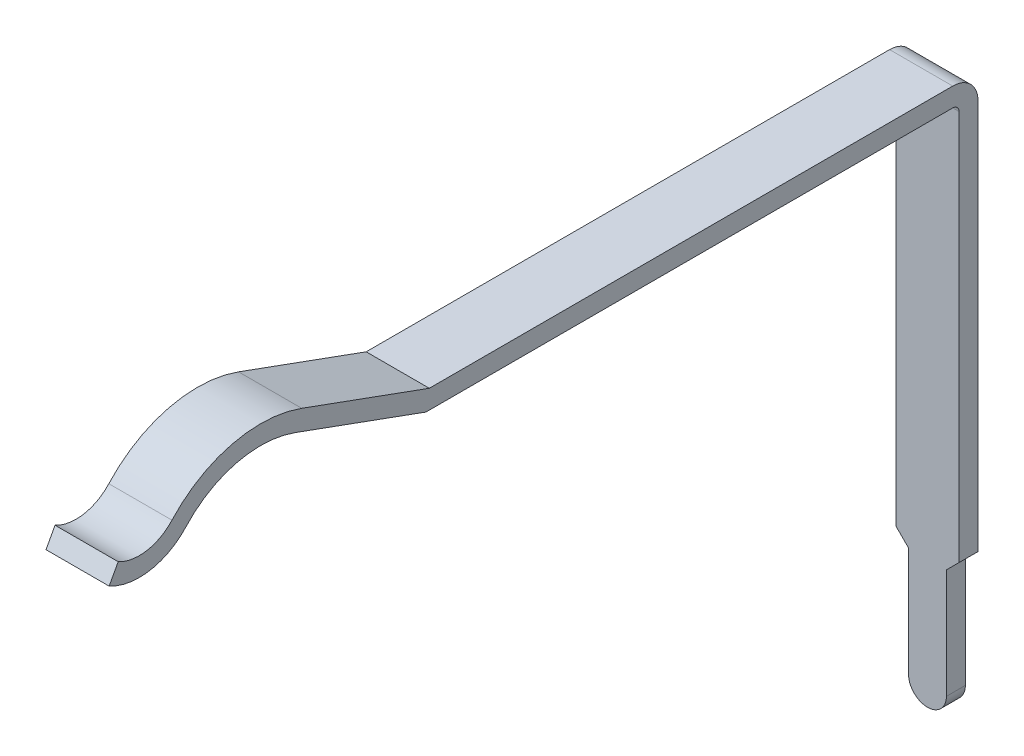
SolidWorks part; units mm, degrees
material "Pure Gold"
ref_plane "Front Plane" through (0, 0, 0) normal (0, 0, 1) x (1, 0, 0)
ref_plane "Top Plane" through (0, 0, 0) normal (0, 1, 0) x (1, 0, 0)
ref_plane "Right Plane" through (0, 0, 0) normal (1, 0, 0) x (0, 0, -1)
sketch "Sketch1" plane through (0, 0, 0) normal (1, 0, 0) x (0, 0, -1)
  line L0 (0, 0.75) -> (36.8303, 0.75) construction
  line L1 (55, 0) -> (-55, 0) construction
  line L2 (0, 55) -> (0, -55) construction
  line L3 (3.9472, 0.7535) -> (6.0175, 0)
  line L4 (6.0175, 0) -> (14.36, 0)
  line L5 (14.46, -0.1) -> (14.46, -8.52)
  line L6 (3.4, 0.85) -> (3.4, 0.75) construction
  arc A0 (3.9472, 0.7535) -> (2.2167, 0.3269) centre (3.4, -0.75) ccw
  arc A1 (14.36, 0) -> (14.46, -0.1) centre (14.36, -0.1) cw
  arc A2 (2.2167, 0.3269) -> (1, 0.1212) centre (1.4771, 1) cw
  dimension "D4" = 0.1
  dimension "D6" = 1
  dimension "D9" = 0.1
  dimension "D1" = 0.75
  dimension "D2" = 3.4
  dimension "D3" = 20
  dimension "D5" = 0.75
  dimension "D7" = 1
  dimension "D8" = 14.46
  dimension "D10" = 8.52
extrude "Extrude-Thin1" add sketch "Sketch1" along normal mid plane 1 thin thin type one direction reverse wall 0.3
sketch "Sketch2" plane through (0, 0, 0) normal (0, 0, 1) x (1, 0, 0)
  line L0 (0, -5.3185) -> (0, 5.3185) construction
  line L1 (0.5, -8.52) -> (-0.5, -8.52) construction
  line L2 (-0.3, -8.22) -> (-0.3, -6.4853)
  line L3 (-0.3, -6.4853) -> (-0.5, -6.2853)
  line L4 (-0.5, -0.1) -> (-0.5, -8.52) construction
  line L5 (-0.5, -6.2853) -> (-0.5, -9.22)
  line L6 (-0.5, -9.22) -> (0.5, -9.22)
  line L7 (0.5, -9.22) -> (0.5, -6.2853)
  line L8 (0.5, -0.1) -> (0.5, -8.52) construction
  line L9 (0.5, -6.2853) -> (0.3, -6.4853)
  line L10 (0.3, -6.4853) -> (0.3, -8.22)
  arc A0 (-0.3, -8.22) -> (0.3, -8.22) centre (0, -8.22) ccw
  dimension "D1" = 0.6
  dimension "D2" = 0.3
  dimension "D3" = 2.0347
  dimension "D4" = 1
  dimension "D5" = 45
extrude "Cut-Extrude1" cut sketch "Sketch2" against normal through all
